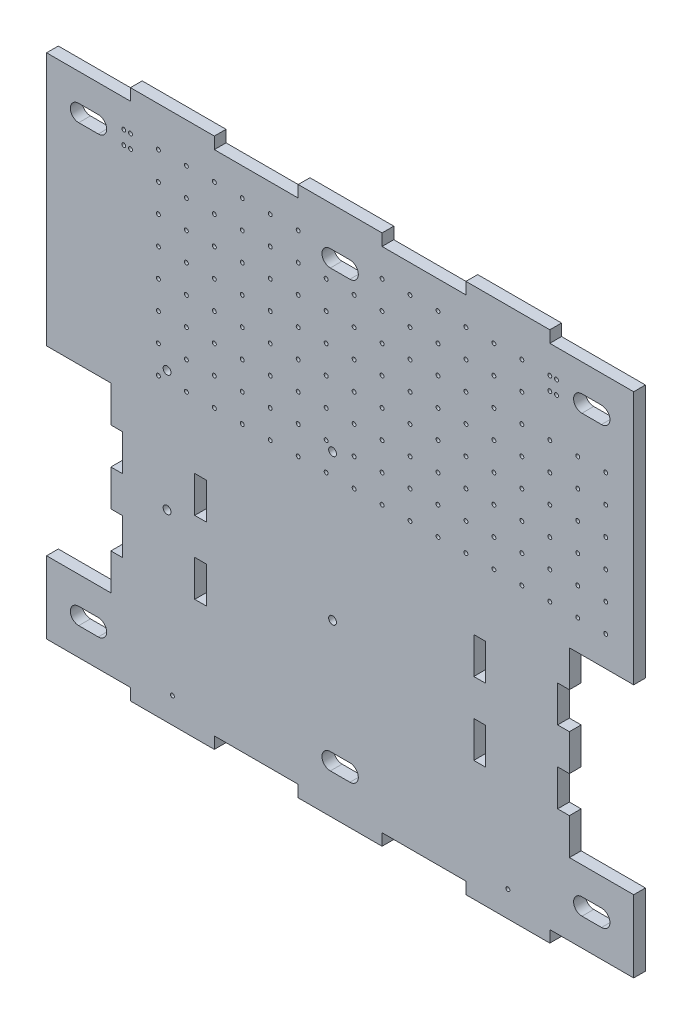
SolidWorks part; units mm, degrees
ref_plane "Front Plane" through (0, 0, 0) normal (0, 0, 1) x (1, 0, 0)
ref_plane "Top Plane" through (0, 0, 0) normal (0, 1, 0) x (1, 0, 0)
ref_plane "Right Plane" through (0, 0, 0) normal (1, 0, 0) x (0, 0, -1)
sketch "Sketch1" plane through (0, 0, 0) normal (0, 0, 1) x (1, 0, 0)
  line L1 (-133.35, 120.65) -> (133.35, 120.65)
  line L2 (-133.35, 120.65) -> (-133.35, -120.65)
  line L3 (-133.35, -120.65) -> (133.35, -120.65)
  line L4 (133.35, 120.65) -> (133.35, -120.65)
  line L5 (-133.35, 120.65) -> (133.35, -120.65) construction
  line L6 (-133.35, -120.65) -> (133.35, 120.65) construction
  point P0 (0, 0)
  dimension "D1" = 241.3
  dimension "D2" = 266.7
extrude "Boss-Extrude1" add sketch "Sketch1" along normal blind 5.334
sketch "Sketch2" plane through (0, 0, 0) normal (0, 0, -1) x (-1, 0, 0)
  line L0 (133.35, 120.65) -> (133.35, -120.65) construction
  line L1 (133.35, 0) -> (104.14, 0)
  line L2 (133.35, 0) -> (133.35, -82.55)
  line L3 (133.35, -82.55) -> (104.14, -82.55)
  line L4 (104.14, 0) -> (104.14, -82.55)
  line L5 (-133.35, -120.65) -> (-133.35, 120.65) construction
  line L6 (-133.35, 0) -> (-104.14, 0)
  line L7 (-133.35, 0) -> (-133.35, -82.55)
  line L8 (-133.35, -82.55) -> (-104.14, -82.55)
  line L9 (-104.14, 0) -> (-104.14, -82.55)
  line L10 (133.35, -120.65) -> (-133.35, -120.65) construction
  dimension "D1" = 82.55
  dimension "D2" = 82.55
  dimension "D3" = 38.1
  dimension "D4" = 38.1
  dimension "D5" = 29.21
  dimension "D6" = 29.21
extrude "Cut-Extrude1" cut sketch "Sketch2" against normal through all
sketch "Sketch9" plane through (0, 0, 5.334) normal (0, 0, 1) x (1, 0, 0)
  line L0 (-104.14, 0) -> (-104.14, -82.55) construction
  line L1 (-104.14, -16.51) -> (-98.806, -16.51)
  line L2 (-104.14, -16.51) -> (-104.14, -33.02)
  line L3 (-104.14, -33.02) -> (-98.806, -33.02)
  line L4 (-98.806, -16.51) -> (-98.806, -33.02)
  line L5 (-104.14, 0) -> (-98.806, 0) construction
  line L6 (-104.14, -49.53) -> (-98.806, -49.53)
  line L7 (-104.14, -49.53) -> (-104.14, -66.04)
  line L8 (-104.14, -66.04) -> (-98.806, -66.04)
  line L9 (-98.806, -49.53) -> (-98.806, -66.04)
  line L10 (-98.806, 0) -> (-98.806, -16.51) construction
  line L11 (-98.806, -33.02) -> (-98.806, -49.53) construction
  line L12 (-104.14, -82.55) -> (-98.806, -82.55) construction
  line L13 (-98.806, -82.55) -> (-98.806, -66.04) construction
  line L14 (0, -120.65) -> (0, 120.65) construction
  line L15 (-133.35, -120.65) -> (133.35, -120.65) construction
  line L16 (133.35, 120.65) -> (-133.35, 120.65) construction
  line L17 (98.806, -82.55) -> (98.806, -66.04) construction
  line L18 (104.14, -82.55) -> (98.806, -82.55) construction
  line L19 (98.806, -33.02) -> (98.806, -49.53) construction
  line L20 (98.806, 0) -> (98.806, -16.51) construction
  line L21 (104.14, 0) -> (98.806, 0) construction
  line L22 (98.806, -49.53) -> (98.806, -66.04)
  line L23 (104.14, -66.04) -> (98.806, -66.04)
  line L24 (104.14, -49.53) -> (104.14, -66.04)
  line L25 (104.14, -49.53) -> (98.806, -49.53)
  line L26 (98.806, -16.51) -> (98.806, -33.02)
  line L27 (104.14, -33.02) -> (98.806, -33.02)
  line L28 (104.14, -16.51) -> (104.14, -33.02)
  line L29 (104.14, -16.51) -> (98.806, -16.51)
  dimension "D1" = 5.334
extrude "Cut-Extrude2" cut sketch "Sketch9" against normal through all
sketch "Sketch23" plane through (0, 0, 5.334) normal (0, 0, 1) x (1, 0, 0)
  line L0 (-98.806, -24.765) -> (-61.976, -24.765) construction
  line L1 (-98.806, -33.02) -> (-98.806, -16.51) construction
  line L2 (-98.806, -16.51) -> (-60.706, -16.51) construction
  line L3 (-98.806, -33.02) -> (-60.706, -33.02) construction
  line L4 (-104.14, -41.275) -> (104.14, -41.275) construction
  line L5 (-104.14, -33.02) -> (-104.14, -49.53) construction
  line L6 (104.14, -49.53) -> (104.14, -33.02) construction
  line L7 (-98.806, -49.53) -> (-60.706, -49.53) construction
  line L8 (-98.806, -57.785) -> (-61.976, -57.785) construction
  line L9 (-98.806, -66.04) -> (-60.706, -66.04) construction
  line L10 (0, -120.65) -> (0, 120.65) construction
  line L11 (-133.35, -120.65) -> (133.35, -120.65) construction
  line L12 (133.35, 120.65) -> (-133.35, 120.65) construction
  line L13 (98.806, -66.04) -> (60.706, -66.04) construction
  line L14 (98.806, -49.53) -> (60.706, -49.53) construction
  line L15 (98.806, -33.02) -> (60.706, -33.02) construction
  line L16 (98.806, -16.51) -> (60.706, -16.51) construction
  line L17 (-60.706, -66.04) -> (-66.04, -66.04)
  line L18 (60.706, -16.51) -> (66.04, -16.51)
  line L19 (60.706, -16.51) -> (60.706, -33.02)
  line L20 (60.706, -33.02) -> (66.04, -33.02)
  line L21 (66.04, -16.51) -> (66.04, -33.02)
  line L22 (60.706, -49.53) -> (66.04, -49.53)
  line L23 (60.706, -49.53) -> (60.706, -66.04)
  line L24 (60.706, -66.04) -> (66.04, -66.04)
  line L25 (66.04, -49.53) -> (66.04, -66.04)
  line L26 (-66.04, -49.53) -> (-66.04, -66.04)
  line L27 (-60.706, -49.53) -> (-60.706, -66.04)
  line L28 (-60.706, -49.53) -> (-66.04, -49.53)
  line L29 (-60.706, -33.02) -> (-66.04, -33.02)
  line L30 (-66.04, -16.51) -> (-66.04, -33.02)
  line L31 (-60.706, -16.51) -> (-66.04, -16.51)
  line L32 (-60.706, -16.51) -> (-60.706, -33.02)
  line L33 (98.806, -16.51) -> (98.806, -33.02) construction
  dimension "D1" = 5.334
  dimension "D2" = 5.334
  dimension "D3" = 32.766
  dimension "D4" = 32.766
extrude "Cut-Extrude8" cut sketch "Sketch23" against normal through all
sketch "Sketch28" plane through (0, 0, 0) normal (0, 0, -1) x (-1, 0, 0)
  line L0 (133.35, -120.65) -> (-133.35, -120.65) construction
  line L1 (-133.35, -120.65) -> (-95.25, -120.65)
  line L2 (-133.35, -120.65) -> (-133.35, -115.316)
  line L3 (-133.35, -115.316) -> (-95.25, -115.316)
  line L4 (-95.25, -120.65) -> (-95.25, -115.316)
  line L5 (-57.15, -120.65) -> (-19.05, -120.65)
  line L6 (-57.15, -120.65) -> (-57.15, -115.316)
  line L7 (-57.15, -115.316) -> (-19.05, -115.316)
  line L8 (-19.05, -120.65) -> (-19.05, -115.316)
  line L9 (133.35, -82.55) -> (133.35, -120.65) construction
  line L10 (19.05, -120.65) -> (57.15, -120.65)
  line L11 (19.05, -120.65) -> (19.05, -115.316)
  line L12 (19.05, -115.316) -> (57.15, -115.316)
  line L13 (57.15, -120.65) -> (57.15, -115.316)
  line L14 (95.25, -120.65) -> (133.35, -120.65)
  line L16 (95.25, -115.316) -> (133.35, -115.316)
  line L17 (133.35, -120.65) -> (133.35, -115.316)
  line L18 (-95.25, -115.316) -> (-57.15, -115.316) construction
  line L19 (-19.05, -115.316) -> (19.05, -115.316) construction
  line L20 (95.25, -115.316) -> (57.15, -115.316) construction
  line L21 (133.35, 120.65) -> (133.35, -115.316) construction
  line L22 (133.35, -115.316) -> (133.5431, -115.1744) construction
  line L41 (95.25, -120.65) -> (95.25, -115.316)
  dimension "D1" = 5.334
extrude "Cut-Extrude13" cut sketch "Sketch28" against normal through all
sketch "Sketch29" plane through (0, 0, 0) normal (0, 0, -1) x (-1, 0, 0)
  line L0 (-133.35, 120.65) -> (133.35, 120.65) construction
  line L1 (-133.35, 120.65) -> (-95.25, 120.65)
  line L2 (-133.35, 120.65) -> (-133.35, 115.316)
  line L3 (-133.35, 115.316) -> (-95.25, 115.316)
  line L4 (-95.25, 120.65) -> (-95.25, 115.316)
  line L5 (-57.15, 120.65) -> (-19.05, 120.65)
  line L6 (-57.15, 120.65) -> (-57.15, 115.316)
  line L7 (-57.15, 115.316) -> (-19.05, 115.316)
  line L8 (-19.05, 120.65) -> (-19.05, 115.316)
  line L9 (133.35, 120.65) -> (133.35, 0) construction
  line L10 (19.05, 120.65) -> (57.15, 120.65)
  line L11 (19.05, 120.65) -> (19.05, 115.316)
  line L12 (19.05, 115.316) -> (57.15, 115.316)
  line L13 (57.15, 120.65) -> (57.15, 115.316)
  line L14 (95.25, 120.65) -> (133.35, 120.65)
  line L15 (95.25, 120.65) -> (95.25, 115.316)
  line L16 (95.25, 115.316) -> (133.35, 115.316)
  line L17 (133.35, 120.65) -> (133.35, 115.316)
  line L18 (-95.25, 115.316) -> (-57.15, 115.316) construction
  line L19 (19.05, 115.316) -> (-19.05, 115.316) construction
  line L20 (57.15, 115.316) -> (95.25, 115.316) construction
  dimension "D1" = 5.334
extrude "Cut-Extrude14" cut sketch "Sketch29" against normal through all
sketch "Sketch30" plane through (0, 0, 5.334) normal (0, 0, 1) x (1, 0, 0)
  line L2 (-44.45, 102.616) -> (-95.25, 102.616) construction
  line L3 (44.45, 102.616) -> (95.25, 102.616) construction
  circle A0 centre (-98.298, 102.616) radius 0.889
  circle A1 centre (-98.298, 96.52) radius 0.889
  circle A2 centre (-95.25, 96.52) radius 0.889
  circle A3 centre (98.298, 102.616) radius 0.889
  circle A4 centre (98.298, 96.52) radius 0.889
  circle A5 centre (95.25, 96.52) radius 0.889
  circle A6 centre (-44.45, 102.616) radius 0.889
  circle A7 centre (-31.75, 102.616) radius 0.889
  circle A8 centre (-19.05, 102.616) radius 0.889
  circle A11 centre (19.05, 102.616) radius 0.889
  circle A12 centre (31.75, 102.616) radius 0.889
  circle A13 centre (44.45, 102.616) radius 0.889
  circle A14 centre (44.45, 102.616) radius 0.889 [skipped]
  circle A15 centre (57.15, 102.616) radius 0.889
  circle A16 centre (-95.25, 102.616) radius 0.889
  circle A17 centre (69.85, 102.616) radius 0.889
  circle A18 centre (82.55, 102.616) radius 0.889
  circle A19 centre (-31.75, 89.916) radius 0.889
  circle A20 centre (-19.05, 89.916) radius 0.889
  circle A21 centre (-6.35, 89.916) radius 0.889
  circle A22 centre (6.35, 89.916) radius 0.889
  circle A23 centre (19.05, 89.916) radius 0.889
  circle A24 centre (31.75, 89.916) radius 0.889
  circle A25 centre (95.25, 102.616) radius 0.889
  circle A26 centre (44.45, 89.916) radius 0.889
  circle A27 centre (57.15, 89.916) radius 0.889
  circle A28 centre (69.85, 89.916) radius 0.889
  circle A29 centre (82.55, 89.916) radius 0.889
  circle A30 centre (-31.75, 77.216) radius 0.889
  circle A31 centre (-19.05, 77.216) radius 0.889
  circle A32 centre (-6.35, 77.216) radius 0.889
  circle A33 centre (6.35, 77.216) radius 0.889
  circle A34 centre (19.05, 77.216) radius 0.889
  circle A35 centre (31.75, 77.216) radius 0.889
  circle A36 centre (44.45, 77.216) radius 0.889
  circle A37 centre (57.15, 77.216) radius 0.889
  circle A38 centre (69.85, 77.216) radius 0.889
  circle A39 centre (82.55, 77.216) radius 0.889
  circle A40 centre (-31.75, 64.516) radius 0.889
  circle A41 centre (-19.05, 64.516) radius 0.889
  circle A42 centre (-6.35, 64.516) radius 0.889
  circle A43 centre (6.35, 64.516) radius 0.889
  circle A44 centre (19.05, 64.516) radius 0.889
  circle A45 centre (31.75, 64.516) radius 0.889
  circle A46 centre (44.45, 64.516) radius 0.889 [skipped]
  circle A47 centre (57.15, 64.516) radius 0.889
  circle A48 centre (69.85, 64.516) radius 0.889
  circle A49 centre (82.55, 64.516) radius 0.889
  circle A50 centre (-31.75, 51.816) radius 0.889
  circle A51 centre (-19.05, 51.816) radius 0.889
  circle A52 centre (-6.35, 51.816) radius 0.889
  circle A53 centre (6.35, 51.816) radius 0.889
  circle A54 centre (19.05, 51.816) radius 0.889
  circle A55 centre (31.75, 51.816) radius 0.889
  circle A56 centre (44.45, 51.816) radius 0.889
  circle A57 centre (57.15, 51.816) radius 0.889
  circle A58 centre (69.85, 51.816) radius 0.889
  circle A59 centre (82.55, 51.816) radius 0.889
  circle A60 centre (-44.45, 64.516) radius 0.889
  circle A61 centre (-31.75, 39.116) radius 0.889
  circle A62 centre (-19.05, 39.116) radius 0.889
  circle A63 centre (-6.35, 39.116) radius 0.889
  circle A64 centre (6.35, 39.116) radius 0.889
  circle A65 centre (19.05, 39.116) radius 0.889
  circle A66 centre (31.75, 39.116) radius 0.889
  circle A67 centre (44.45, 64.516) radius 0.889
  circle A68 centre (44.45, 39.116) radius 0.889
  circle A69 centre (57.15, 39.116) radius 0.889
  circle A70 centre (69.85, 39.116) radius 0.889
  circle A71 centre (82.55, 39.116) radius 0.889
  circle A72 centre (-44.45, 89.916) radius 0.889
  circle A73 centre (-44.45, 77.216) radius 0.889
  circle A74 centre (-44.45, 64.516) radius 0.889 [skipped]
  circle A75 centre (-44.45, 51.816) radius 0.889
  circle A76 centre (-44.45, 39.116) radius 0.889
  circle A77 centre (-57.15, 102.616) radius 0.889
  circle A78 centre (-69.85, 102.616) radius 0.889
  circle A79 centre (-82.55, 102.616) radius 0.889
  circle A80 centre (-57.15, 89.916) radius 0.889
  circle A81 centre (-69.85, 89.916) radius 0.889
  circle A82 centre (-82.55, 89.916) radius 0.889
  circle A83 centre (-57.15, 77.216) radius 0.889
  circle A84 centre (-69.85, 77.216) radius 0.889
  circle A85 centre (-82.55, 77.216) radius 0.889
  circle A86 centre (-57.15, 64.516) radius 0.889
  circle A87 centre (-69.85, 64.516) radius 0.889
  circle A88 centre (-82.55, 64.516) radius 0.889
  circle A89 centre (-57.15, 51.816) radius 0.889
  circle A90 centre (-69.85, 51.816) radius 0.889
  circle A91 centre (-82.55, 51.816) radius 0.889
  circle A92 centre (-57.15, 39.116) radius 0.889
  circle A93 centre (-69.85, 39.116) radius 0.889
  circle A94 centre (-82.55, 39.116) radius 0.889
  circle A95 centre (-44.45, 89.916) radius 0.889 [skipped]
  circle A96 centre (-44.45, 77.216) radius 0.889 [skipped]
  circle A97 centre (-44.45, 64.516) radius 0.889 [skipped]
  circle A98 centre (-44.45, 51.816) radius 0.889 [skipped]
  circle A99 centre (-44.45, 39.116) radius 0.889 [skipped]
  circle A100 centre (95.25, 77.216) radius 0.889
  circle A101 centre (107.95, 77.216) radius 0.889
  circle A102 centre (120.65, 77.216) radius 0.889
  circle A103 centre (95.25, 64.516) radius 0.889
  circle A104 centre (107.95, 64.516) radius 0.889
  circle A105 centre (120.65, 64.516) radius 0.889
  circle A106 centre (95.25, 51.816) radius 0.889
  circle A107 centre (107.95, 51.816) radius 0.889
  circle A108 centre (120.65, 51.816) radius 0.889
  circle A109 centre (95.25, 39.116) radius 0.889
  circle A110 centre (107.95, 39.116) radius 0.889
  circle A111 centre (120.65, 39.116) radius 0.889
  circle A112 centre (95.25, 26.416) radius 0.889
  circle A113 centre (107.95, 26.416) radius 0.889
  circle A114 centre (120.65, 26.416) radius 0.889
  circle A115 centre (95.25, 13.716) radius 0.889
  circle A116 centre (107.95, 13.716) radius 0.889
  circle A117 centre (120.65, 13.716) radius 0.889
  circle A118 centre (82.55, 64.516) radius 0.889 [skipped]
  circle A119 centre (82.55, 51.816) radius 0.889 [skipped]
  circle A120 centre (82.55, 39.116) radius 0.889 [skipped]
  circle A121 centre (82.55, 26.416) radius 0.889
  circle A122 centre (82.55, 13.716) radius 0.889
  circle A123 centre (69.85, 26.416) radius 0.889
  circle A124 centre (69.85, 13.716) radius 0.889
  circle A125 centre (57.15, 26.416) radius 0.889
  circle A126 centre (57.15, 13.716) radius 0.889
  circle A127 centre (44.45, 26.416) radius 0.889
  circle A128 centre (44.45, 13.716) radius 0.889
  circle A129 centre (31.75, 26.416) radius 0.889
  circle A130 centre (31.75, 13.716) radius 0.889
  circle A131 centre (19.05, 26.416) radius 0.889
  circle A132 centre (19.05, 13.716) radius 0.889
  circle A133 centre (6.35, 26.416) radius 0.889
  circle A134 centre (6.35, 13.716) radius 0.889
  circle A135 centre (-6.35, 26.416) radius 0.889
  circle A136 centre (-6.35, 13.716) radius 0.889
  circle A137 centre (-19.05, 26.416) radius 0.889
  circle A138 centre (-19.05, 13.716) radius 0.889
  circle A139 centre (-31.75, 26.416) radius 0.889
  circle A140 centre (-31.75, 13.716) radius 0.889
  circle A141 centre (-44.45, 26.416) radius 0.889
  circle A142 centre (-44.45, 13.716) radius 0.889
  circle A143 centre (-57.15, 26.416) radius 0.889
  circle A144 centre (-57.15, 13.716) radius 0.889
  circle A145 centre (-69.85, 26.416) radius 0.889
  circle A146 centre (-69.85, 13.716) radius 0.889
  circle A147 centre (-82.55, 26.416) radius 0.889
  circle A148 centre (-82.55, 13.716) radius 0.889
  circle A149 centre (6.35, 102.616) radius 0.889 [skipped]
  circle A150 centre (-6.35, 102.616) radius 0.889 [skipped]
  dimension "D1" = 2
  dimension "D2" = 88.9
  dimension "D3" = 38.1
  dimension "D6" = 2
  dimension "D5" = 11
  dimension "D7" = 50.8
  dimension "D10" = 6
  dimension "D9" = 50.8
  dimension "D12" = 6
  dimension "D8" = 2
  dimension "D4" = 2
  dimension "D11" = 4
  dimension "D13" = 4
  dimension "D14" = 6
  dimension "D15" = 14
extrude "Cut-Extrude15" cut sketch "Sketch30" against normal through all
sketch "Sketch32" plane through (0, 0, 0) normal (0, 0, -1) x (-1, 0, 0)
  circle A0 centre (3.4305, -42.9775) radius 1.778 construction
  circle A1 centre (78.6145, -37.1355) radius 1.778 construction
  circle A2 centre (3.4305, 23.3165) radius 1.778 construction
  circle A3 centre (78.6145, 17.7285) radius 1.778 construction
  circle A4 centre (3.4305, -42.9775) radius 1.778
  circle A5 centre (78.6145, -37.1355) radius 1.778
  circle A6 centre (3.4305, 23.3165) radius 1.778
  circle A7 centre (78.6145, 17.7285) radius 1.778
extrude "Cut-Extrude16" cut sketch "Sketch32" against normal through all
sketch "Sketch35" plane through (0, 0, 5.334) normal (0, 0, 1) x (1, 0, 0)
  line L0 (0, 120.65) -> (0, -120.65) construction
  line L1 (19.05, 120.65) -> (-19.05, 120.65) construction
  line L2 (-19.05, -120.65) -> (19.05, -120.65) construction
  line L3 (-133.35, -98.933) -> (133.35, -98.933) construction
  line L4 (-133.35, -82.55) -> (-133.35, -115.316) construction
  line L5 (133.35, -115.316) -> (133.35, -82.55) construction
  line L6 (-118.745, -82.55) -> (-118.745, -115.316) construction
  line L7 (-104.14, -82.55) -> (-133.35, -82.55) construction
  line L8 (-133.35, -115.316) -> (-95.25, -115.316) construction
  line L9 (-114.3, -115.316) -> (-114.3, -82.55) construction
  line L10 (118.745, -82.55) -> (118.745, -115.316) construction
  line L11 (133.35, -82.55) -> (104.14, -82.55) construction
  line L12 (95.25, -115.316) -> (133.35, -115.316) construction
  line L13 (114.3, -115.316) -> (114.3, -82.55) construction
  line L14 (-109.855, -98.933) -> (-118.745, -98.933) construction
  line L15 (-109.855, -102.743) -> (-118.745, -102.743)
  line L16 (-109.855, -95.123) -> (-118.745, -95.123)
  line L17 (109.855, -98.933) -> (118.745, -98.933) construction
  line L18 (109.855, -95.123) -> (118.745, -95.123)
  line L19 (109.855, -102.743) -> (118.745, -102.743)
  line L20 (0, 0) -> (43.5068, 0) construction
  line L21 (109.855, 98.933) -> (118.745, 98.933) construction
  line L22 (109.855, 95.123) -> (118.745, 95.123)
  line L23 (109.855, 102.743) -> (118.745, 102.743)
  line L24 (-109.855, 98.933) -> (-118.745, 98.933) construction
  line L25 (-109.855, 102.743) -> (-118.745, 102.743)
  line L26 (-109.855, 95.123) -> (-118.745, 95.123)
  line L27 (4.445, 98.933) -> (-4.445, 98.933) construction
  line L28 (4.445, 102.743) -> (-4.445, 102.743)
  line L29 (4.445, 95.123) -> (-4.445, 95.123)
  line L30 (4.445, -98.933) -> (-4.445, -98.933) construction
  line L31 (4.445, -102.743) -> (-4.445, -102.743)
  line L32 (4.445, -95.123) -> (-4.445, -95.123)
  arc A0 (-109.855, -102.743) -> (-109.855, -95.123) centre (-109.855, -98.933) ccw
  arc A1 (-118.745, -95.123) -> (-118.745, -102.743) centre (-118.745, -98.933) ccw
  arc A2 (109.855, -95.123) -> (109.855, -102.743) centre (109.855, -98.933) ccw
  arc A3 (118.745, -102.743) -> (118.745, -95.123) centre (118.745, -98.933) ccw
  arc A4 (109.855, 95.123) -> (109.855, 102.743) centre (109.855, 98.933) cw
  arc A5 (118.745, 102.743) -> (118.745, 95.123) centre (118.745, 98.933) cw
  arc A6 (-109.855, 102.743) -> (-109.855, 95.123) centre (-109.855, 98.933) cw
  arc A7 (-118.745, 95.123) -> (-118.745, 102.743) centre (-118.745, 98.933) cw
  arc A8 (4.445, 102.743) -> (4.445, 95.123) centre (4.445, 98.933) cw
  arc A9 (-4.445, 95.123) -> (-4.445, 102.743) centre (-4.445, 98.933) cw
  arc A10 (4.445, -102.743) -> (4.445, -95.123) centre (4.445, -98.933) ccw
  arc A11 (-4.445, -95.123) -> (-4.445, -102.743) centre (-4.445, -98.933) ccw
  point P30 (-114.3, -98.933)
  point P36 (114.3, -98.933)
  point P47 (114.3, 98.933)
  point P54 (-114.3, 98.933)
  point P63 (0, 98.933)
  point P70 (0, -98.933)
  dimension "D1" = 2
  dimension "D2" = 2
extrude "Cut-Extrude19" cut sketch "Sketch35" against normal through all
sketch "Sketch36" plane through (0, 0, 0) normal (0, 0, -1) x (-1, 0, 0)
  line L0 (-19.05, -115.316) -> (-57.15, -115.316) construction
  line L1 (-76.2, -120.65) -> (-76.2, -93.1293) construction
  line L2 (-57.15, -120.65) -> (-95.25, -120.65) construction
  line L3 (0, -120.65) -> (0, -86.5678) construction
  line L4 (19.05, -120.65) -> (-19.05, -120.65) construction
  circle A0 centre (-76.2, -108.966) radius 0.889
  circle A1 centre (76.2, -108.966) radius 0.889
  dimension "D1" = 1.778
  dimension "D2" = 6.35
  dimension "D3" = 0
extrude "Cut-Extrude20" cut sketch "Sketch36" against normal through all
equation "\"MDF\"= .21in"
equation "\"Foamcore\"= .13in"
equation "\"Gmaterial\"= \"MDF\""
equation "\"D1@Sketch9\"=\"MDF\""
equation "\"D1@Sketch23\"=\"MDF\""
equation "\"D2@Sketch23\"=\"D1@Sketch23\""
equation "\"D1@Boss-Extrude1\"=\"MDF\""
equation "\"D3@Sketch23\"=1.29"
equation "\"D1@Sketch28\"=\"MDF\""
equation "\"D1@Sketch29\"=\"MDF\""
